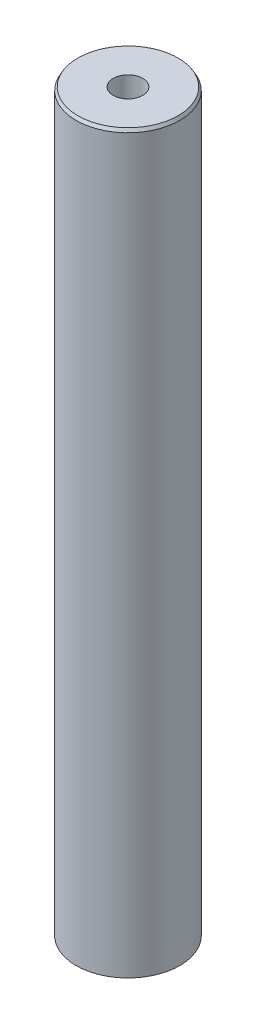
SolidWorks part; units mm, degrees
ref_plane "Front Plane" through (0, 0, 0) normal (0, 0, 1) x (1, 0, 0)
ref_plane "Top Plane" through (0, 0, 0) normal (0, 1, 0) x (1, 0, 0)
ref_plane "Right Plane" through (0, 0, 0) normal (1, 0, 0) x (0, 0, -1)
sketch "Sketch1" plane through (0, 0, 0) normal (0, 1, 0) x (1, 0, 0)
  circle A0 centre (0, 0) radius 40
  dimension "SHAFT_OD" = 80
extrude "Boss-Extrude1" add sketch "Sketch1" along normal blind 568.3367
sketch "Sketch2" plane through (0, 0, 0) normal (0, 1, 0) x (1, 0, 0)
  circle A0 centre (0, 0) radius 11.4164
  dimension "BORE_D" = 22.8328
extrude "Cut-Extrude1" cut sketch "Sketch2" along normal through all
chamfer "Chamfer1" distance 2.3985 angle 30 2 edges at (0, 568.3367, 40) (0, 0, 40) first distance on face at (0, 568.3367, 40) first distance on face at (0, 0, 11.4164)
